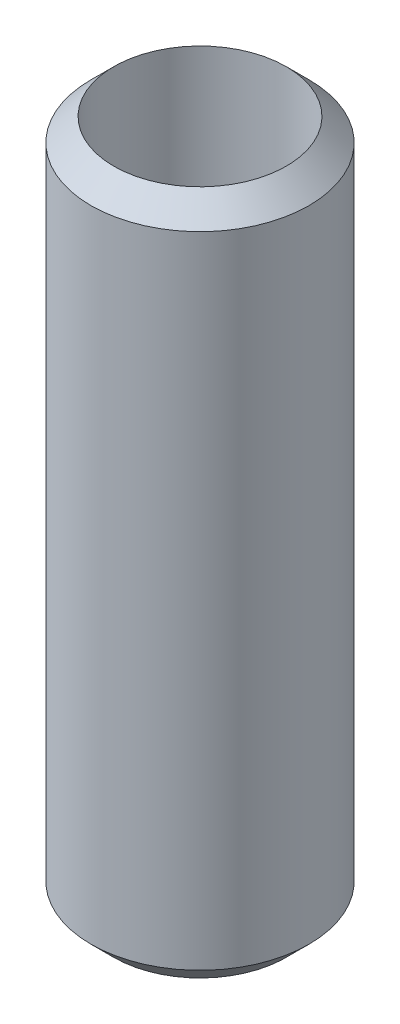
SolidWorks part; units mm, degrees
ref_plane "Front Plane" through (0, 0, 0) normal (0, 0, 1) x (1, 0, 0)
ref_plane "Top Plane" through (0, 0, 0) normal (0, 1, 0) x (1, 0, 0)
ref_plane "Right Plane" through (0, 0, 0) normal (1, 0, 0) x (0, 0, -1)
sketch "Sketch1" plane through (0, 0, 0) normal (0, 1, 0) x (1, 0, 0)
  circle A0 centre (0, 0) radius 22.5
  dimension "SHAFT_OD" = 45
extrude "Boss-Extrude1" add sketch "Sketch1" along normal blind 141.7398
sketch "Sketch2" plane through (0, 0, 0) normal (0, 1, 0) x (1, 0, 0)
  circle A0 centre (0, 0) radius 17.8036
  dimension "BORE_D" = 35.6072
extrude "Cut-Extrude1" cut sketch "Sketch2" along normal through all
chamfer "Chamfer1" distance 4.8576 angle 45 2 edges at (0, 141.7398, 22.5) (0, 0, 22.5)
